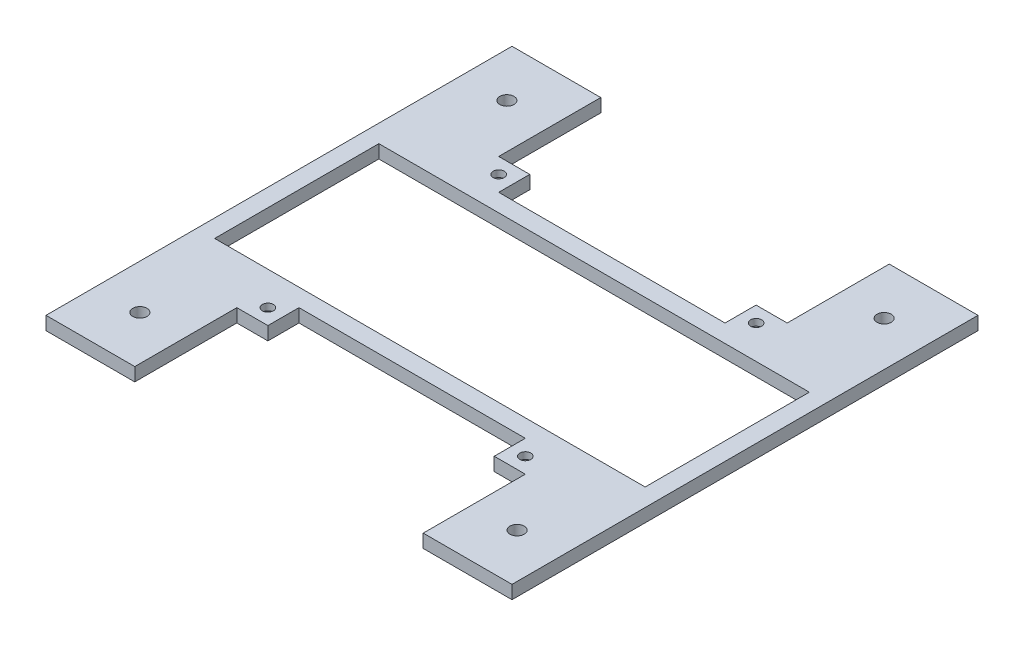
SolidWorks part; units mm, degrees
ref_plane "前视基准面" through (0, 0, 0) normal (0, 0, 1) x (1, 0, 0)
ref_plane "上视基准面" through (0, 0, 0) normal (0, 1, 0) x (1, 0, 0)
ref_plane "右视基准面" through (0, 0, 0) normal (1, 0, 0) x (0, 0, -1)
other "Configuration Table"
sketch "草图1" plane through (0, 0, 0) normal (0, 1, 0) x (1, 0, 0)
  line L0 (82.5, -72.5) -> (82.5, -42.5) construction
  line L9 (-2.5, 32.5) -> (17.5, 32.5)
  line L10 (-2.5, 32.5) -> (-2.5, -72.5)
  line L23 (-2.5, -72.5) -> (17.5, -72.5)
  line L24 (17.5, 32.5) -> (17.5, -72.5)
  line L25 (82.5, -72.5) -> (102.5, -72.5)
  line L26 (82.5, -72.5) -> (82.5, 32.5)
  line L27 (82.5, 32.5) -> (102.5, 32.5)
  line L28 (102.5, -72.5) -> (102.5, 32.5)
  line L29 (24.5, 9.5) -> (17.5, 2.5) construction
  line L30 (1.5, -1.5) -> (98.5, -1.5)
  line L31 (17.5, -42.5) -> (82.5, -42.5)
  line L32 (17.5, -42.5) -> (17.5, 2.5)
  line L33 (17.5, 2.5) -> (82.5, 2.5)
  line L34 (82.5, -42.5) -> (82.5, 2.5)
  line L35 (24.5, 9.5) -> (17.5, 9.5)
  line L36 (24.5, 9.5) -> (24.5, -49.5)
  line L37 (24.5, -49.5) -> (17.5, -49.5)
  line L38 (17.5, 9.5) -> (17.5, -49.5)
  line L39 (75.5, -49.5) -> (82.5, -49.5)
  line L40 (75.5, -49.5) -> (75.5, 9.5)
  line L41 (75.5, 9.5) -> (82.5, 9.5)
  line L42 (82.5, -49.5) -> (82.5, 9.5)
  line L43 (1.5, -1.5) -> (1.5, -38.5)
  line L44 (1.5, -38.5) -> (98.5, -38.5)
  line L45 (98.5, -1.5) -> (98.5, -38.5)
  line L46 (75.5, 9.5) -> (82.5, 2.5) construction
  line L47 (24.5, -49.5) -> (17.5, -42.5) construction
  line L48 (75.5, -49.5) -> (82.5, -42.5) construction
  circle A0 centre (21, 6) radius 2
  circle A1 centre (21, 6) radius 1.25
  circle A2 centre (79, 6) radius 2
  circle A3 centre (79, 6) radius 1.25
  circle A4 centre (79, -46) radius 2
  circle A5 centre (79, -46) radius 1.25
  circle A6 centre (21, -46) radius 2
  circle A7 centre (21, -46) radius 1.25
  circle A8 centre (7.5, 21.35) radius 1.6
  circle A9 centre (92.5, 21.35) radius 1.6
  circle A10 centre (92.5, -61.35) radius 1.6
  circle A11 centre (7.5, -61.35) radius 1.6
  dimension "D12" = 2.5
  dimension "D13" = 4
  dimension "D14" = 3.2
  dimension "D1" = 2.5
  dimension "D2" = 32.5
  dimension "D3" = 105
  dimension "D4" = 20
  dimension "D5" = 7
  dimension "D6" = 7
  dimension "D7" = 7
  dimension "D8" = 4
  dimension "D9" = 4
  dimension "D10" = 4
  dimension "D11" = 4
extrude "凸台-拉伸2" add sketch "草图1" along normal blind 3 contours L24 L23 L10 L9 | L36 L37 L38 L35 | L40 L41 L42 L39 | L28 L27 L26 L25 | L31 L34 L33 L32
extrude "切除-拉伸1" cut sketch "草图1<5>" along normal through all contours L44 L45 L30 L43
sketch "草图1<5>" plane through (0, 0, 0) normal (0, 1, 0) x (1, 0, 0) same geometry as "草图1"
extrude "切除-拉伸3" cut sketch "草图1<6>" along normal through all contours A1 | A7 | A5 | A3 | A8 | A9 | A10 | A11
sketch "草图1<6>" plane through (0, 0, 0) normal (0, 1, 0) x (1, 0, 0) same geometry as "草图1"
extrude "切除-拉伸4" cut sketch "草图1<7>" along normal blind 1.5 contours A0 | A2 | A6 | A4
sketch "草图1<7>" plane through (0, 0, 0) normal (0, 1, 0) x (1, 0, 0) same geometry as "草图1"
